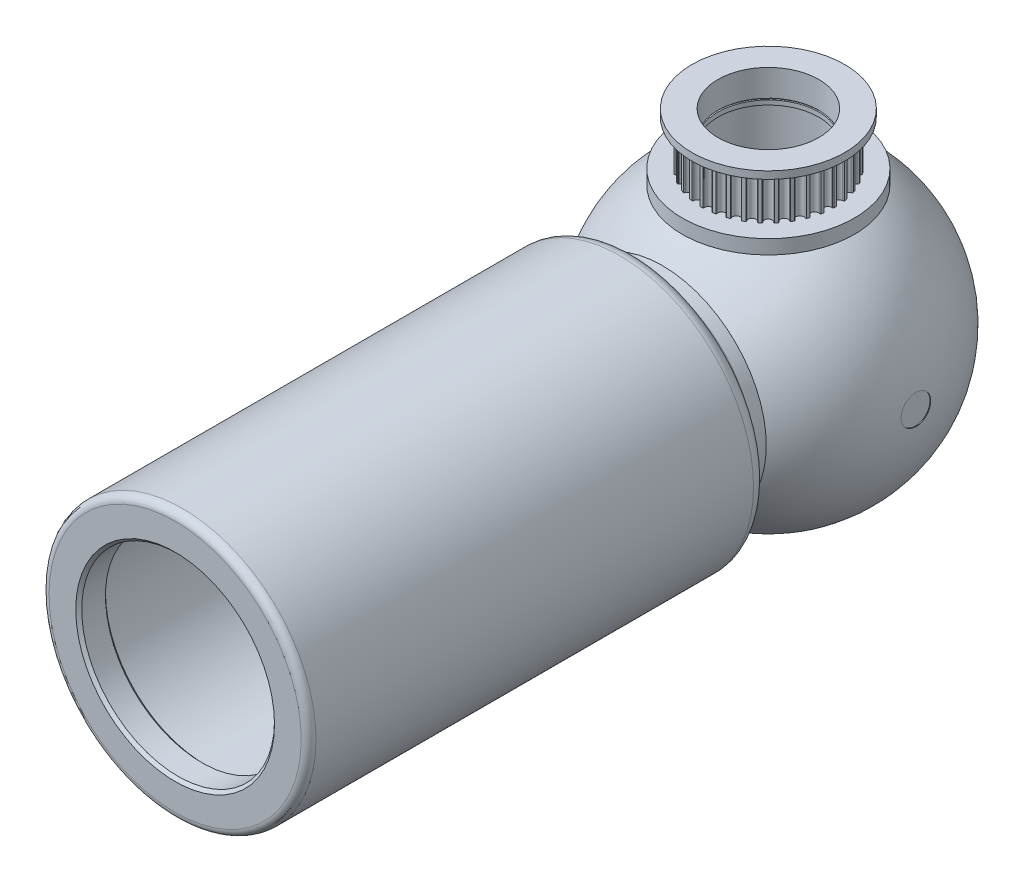
SolidWorks part; units mm, degrees
material "合金钢"
ref_plane "前视基准面" through (0, 0, 0) normal (0, 0, 1) x (1, 0, 0)
ref_plane "上视基准面" through (0, 0, 0) normal (0, 1, 0) x (1, 0, 0)
ref_plane "右视基准面" through (0, 0, 0) normal (1, 0, 0) x (0, 0, -1)
sketch "Sketch1" plane through (0, 0, 0) normal (0, 0, 1) x (1, 0, 0)
  line L1 (58, 81.4616) -> (58, 91.0045)
  line L2 (58, 91.0045) -> (0, 91.0045)
  line L4 (0, -100) -> (0, -130.7878) construction
  line L9 (0, 91.0045) -> (0, -100)
  arc A0 (0, -100) -> (58, 81.4616) centre (0, 0) ccw
  dimension "D1" = 200
  dimension "D2" = 116
  dimension "D3" = 191.0045
revolve "Revolve1" add sketch "Sketch1" angle 360 about L9
sketch "Sketch4" plane through (0, 91.0045, 0) normal (0, 1, 0) x (1, 0, 0)
  circle A0 centre (0, 0) radius 45.15
  dimension "D1" = 90.3
extrude "Extrude3" add sketch "Sketch4" along normal blind 30
sketch "Sketch3" plane through (0, 91.0045, 0) normal (0, 1, 0) x (1, 0, 0)
  line L0 (0, 0) -> (0, 45.835) construction
  line L1 (-3.9948, 45.6606) -> (0, 0) construction
  line L2 (-1.2656, 44.3946) -> (-1.2821, 43.9222)
  line L3 (-6.4627, 43.9399) -> (-6.3644, 43.4775)
  circle A0 centre (0, 0) radius 45.835 construction
  arc A1 (-0.4946, 45.1473) -> (-7.3526, 44.5473) centre (0, 0) ccw
  arc A2 (-6.3644, 43.4775) -> (-1.2821, 43.9222) centre (-3.8505, 44.0119) ccw
  arc A3 (-0.4946, 45.1473) -> (-1.2656, 44.3946) centre (-0.4861, 44.3673) ccw
  arc A4 (-7.3526, 44.5473) -> (-6.4627, 43.9399) centre (-7.2256, 43.7777) cw
  point P4 (44.2732, 11.863)
  point P6 (41.5406, 19.3707)
  point P7 (37.5458, 26.2899)
  point P8 (32.4102, 32.4102)
  point P9 (26.2899, 37.5458)
  point P10 (19.3707, 41.5406)
  point P11 (11.863, 44.2732)
  point P12 (3.9948, 45.6606)
  point P13 (-3.9948, 45.6606)
  point P14 (-11.863, 44.2732)
  point P15 (-19.3707, 41.5406)
  point P16 (-26.2899, 37.5458)
  point P17 (-32.4102, 32.4102)
  point P18 (-37.5458, 26.2899)
  point P19 (-41.5406, 19.3707)
  point P20 (-44.2732, 11.863)
  point P21 (-45.6606, 3.9948)
  point P22 (-45.6606, -3.9948)
  point P23 (-44.2732, -11.863)
  point P24 (-41.5406, -19.3707)
  point P25 (-37.5458, -26.2899)
  point P26 (-32.4102, -32.4102)
  point P27 (-26.2899, -37.5458)
  point P28 (-19.3707, -41.5406)
  point P29 (-11.863, -44.2732)
  point P30 (-3.9948, -45.6606)
  point P31 (3.9948, -45.6606)
  point P32 (11.863, -44.2732)
  point P33 (19.3707, -41.5406)
  point P34 (26.2899, -37.5458)
  point P35 (32.4102, -32.4102)
  point P36 (37.5458, -26.2899)
  point P37 (41.5406, -19.3707)
  point P38 (44.2732, -11.863)
  point P39 (45.6606, -3.9948)
  point P40 (45.6606, 3.9948)
  dimension "D1" = 91.67
  dimension "D2" = 90.3
  dimension "D3" = 5.14
  dimension "D4" = 3.54
  dimension "D5" = 1.56
  dimension "D6" = 7
extrude "Extrude4" cut sketch "Sketch3" along normal up to surface (30 mm away) up to face at (-45.15, 121.0045, 0)
pattern_circular "CirPattern1" count 36 over 360 about axis through (0.0093, 0, 0.1061) along (0, 1, 0) of "Extrude4"
sketch "Sketch5" plane through (0, 121.0045, 0) normal (0, 1, 0) x (1, 0, 0)
  circle A0 centre (0, 0) radius 51.5
  dimension "D1" = 103
extrude "Extrude5" add sketch "Sketch5" along normal blind 5
sketch "Sketch9" plane through (0, 0, 0) normal (1, 0, 0) x (0, 0, -1)
  line L0 (0, -100) -> (0, -129.5943) construction
  line L1 (0, -73.7496) -> (31, -73.7496)
  line L2 (31, -73.7496) -> (31, -71.7496)
  line L3 (31, -71.7496) -> (34, -71.7496)
  line L4 (34, -71.7496) -> (34, -56.7496)
  line L5 (34, -56.7496) -> (35, -56.7496)
  line L6 (35, -56.7496) -> (35, -55.7496)
  line L7 (35, -55.7496) -> (34, -55.7496)
  line L8 (34, -55.7496) -> (34, -52.7496)
  line L9 (34, -52.7496) -> (36, -52.7496)
  line L11 (0, -73.7496) -> (0, 126.0045)
  line L12 (0, 126.0045) -> (34, 126.0045)
  line L13 (51.5, 126.0045) -> (-51.5, 126.0045) construction
  line L14 (36, -52.7496) -> (36, 104.0045)
  line L15 (36, 104.0045) -> (34, 104.0045)
  line L16 (34, 104.0045) -> (34, 107.0045)
  line L17 (34, 107.0045) -> (35, 107.0045)
  line L18 (35, 107.0045) -> (35, 108.0045)
  line L19 (35, 108.0045) -> (34, 108.0045)
  line L20 (34, 108.0045) -> (34, 126.0045)
  arc A0 (-58, 81.4616) -> (58, 81.4616) centre (0, 0) ccw construction
  dimension "D5" = 20
  dimension "D1" = 68
  dimension "D2" = 62
  dimension "D3" = 15
  dimension "D4" = 2
  dimension "D6" = 1
  dimension "D7" = 3
  dimension "D8" = 18
  dimension "D9" = 1
  dimension "D10" = 3
  dimension "D11" = 72
  dimension "D12" = 68
revolve "Cut-Revolve1" cut sketch "Sketch9" angle 360 about L11
ref_plane "Plane2" through (0, 108.5045, 0) normal (0, 1, 0) x (1, 0, 0)
ref_plane "Plane3" through (0, 0, 100) normal (0, 0, 1) x (1, 0, 0)
sketch "Sketch11" plane through (0, 0, 100) normal (0, 0, 1) x (1, 0, 0)
  circle A0 centre (0, 0) radius 70
  dimension "D1" = 140
extrude "Extrude6" add sketch "Sketch11" against normal up to next
sketch "Sketch12" plane through (0, 0, 100) normal (0, 0, 1) x (1, 0, 0)
  circle A0 centre (0, 0) radius 90
  dimension "D1" = 180
extrude "Extrude7" add sketch "Sketch12" against normal blind 10
sketch "Sketch13" plane through (0, 0, 100) normal (0, 0, 1) x (1, 0, 0)
  circle A0 centre (0, 0) radius 75
  circle A1 centre (0, 0) radius 90
  circle A2 centre (0, 0) radius 90
  dimension "D2" = 150
  dimension "D1" = 0
extrude "Extrude8" add sketch "Sketch13" along normal blind 300
fillet "Fillet1" radius 10 2 edges at (90, 0, 90) (70, 0, 90)
sketch "Sketch14" plane through (0, 0, 400) normal (0, 0, 1) x (1, 0, 0)
  circle A0 centre (0, 0) radius 65
  circle A1 centre (0, 0) radius 75
  circle A2 centre (0, 0) radius 75
  dimension "D2" = 130
  dimension "D1" = 0
extrude "Extrude9" add sketch "Sketch14" against normal blind 20
fillet "Fillet2" radius 5 1 edges at (90, 0, 400)
chamfer "Chamfer2" distance 2 angle 45 2 edges at (65, 0, 400) (65, 0, 380)
ref_plane "Plane4" through (100, 0, 0) normal (1, 0, 0) x (0, 0, -1)
sketch "Sketch15" plane through (100, 0, 0) normal (1, 0, 0) x (0, 0, -1)
  circle A0 centre (0, 0) radius 10
  dimension "D1" = 20
extrude "Cut-Extrude1" cut sketch "Sketch15" against normal blind 1
